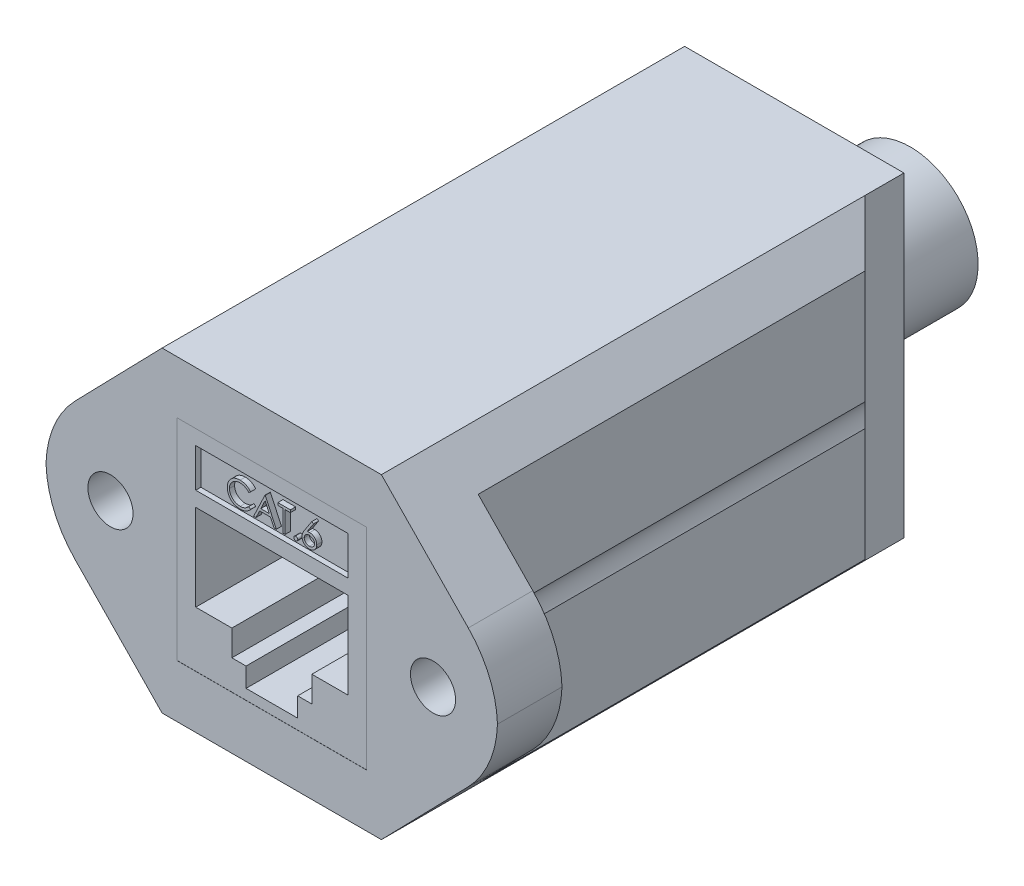
SolidWorks part; units mm, degrees
ref_plane "Front Plane" through (0, 0, 0) normal (0, 0, 1) x (1, 0, 0)
ref_plane "Top Plane" through (0, 0, 0) normal (0, 1, 0) x (1, 0, 0)
ref_plane "Right Plane" through (0, 0, 0) normal (1, 0, 0) x (0, 0, -1)
sketch "Sketch2" plane through (0, 0, 0) normal (0, 0, 1) x (1, 0, 0)
  line L0 (0, 0) -> (0, 24.5) construction
  line L1 (0, 24.5) -> (35, 24.5) construction
  line L2 (35, 24.5) -> (35, 0) construction
  line L3 (35, 0) -> (0, 0) construction
  line L4 (9, 0) -> (0, 9.25)
  line L5 (0, 9.25) -> (0, 15.25)
  line L6 (0, 15.25) -> (9, 24.5)
  line L7 (9, 24.5) -> (26, 24.5)
  line L8 (26, 24.5) -> (35, 15.25)
  line L9 (35, 15.25) -> (35, 9.25)
  line L10 (35, 9.25) -> (26, 0)
  line L11 (26, 0) -> (9, 0)
  line L12 (17.5, 24.5) -> (17.5, 0) construction
  line L13 (0, 12.25) -> (35, 12.25) construction
  dimension "D1" = 24.5
  dimension "D2" = 35
  dimension "D3" = 17
  dimension "D4" = 6
extrude "Boss-Extrude1" add sketch "Sketch2" along normal blind 5
fillet "Fillet1" radius 8 4 edges at (35, 9.25, 2.5) (35, 15.25, 2.5) (0, 9.25, 2.5) (0, 15.25, 2.5)
sketch "Sketch4" plane through (0, 0, 0) normal (0, 0, -1) x (-1, 0, 0)
  line L0 (-17.5, 24.5) -> (-17.5, 0) construction
  line L1 (-26, 24.5) -> (-9, 24.5) construction
  line L2 (-9, 0) -> (-26, 0) construction
  line L3 (-32.7338, 17.5791) -> (-26, 24.5) construction
  line L5 (-28.5, 21.9306) -> (-28.5, 2.5694)
  line L7 (-6.5, 21.9306) -> (-6.5, 2.5694)
  line L9 (-9, 24.5) -> (-2.2662, 17.5791) construction
  line L10 (-26, 0) -> (-32.7338, 6.9209) construction
  line L11 (-28.5, 21.9306) -> (-26, 24.5)
  line L12 (-26, 24.5) -> (-9, 24.5)
  line L13 (-9, 24.5) -> (-6.5, 21.9306)
  line L14 (-28.5, 2.5694) -> (-26, 0)
  line L15 (-26, 0) -> (-9, 0)
  line L16 (-9, 0) -> (-6.5, 2.5694)
  dimension "D1" = 22
extrude "Boss-Extrude2" add sketch "Sketch4" along normal blind 30
sketch "Sketch5" plane through (0, 0, -30) normal (0, 0, -1) x (-1, 0, 0)
  line L0 (-9, 24.5) -> (-26, 24.5) construction
  line L1 (-26, 0) -> (-9, 0) construction
  line L2 (-9, 24.5) -> (-26, 24.5)
  line L3 (-26, 0) -> (-9, 0)
  line L4 (-26, 0) -> (-26, 24.5)
  line L5 (-9, 0) -> (-9, 24.5)
extrude "Boss-Extrude3" add sketch "Sketch5" along normal blind 5.5
chamfer "Chamfer2" distance 2.5 angle 45 2 edges at (9, 12.25, -30) (26, 12.25, -30)
sketch "Sketch6" plane through (0, 0, -35.5) normal (0, 0, -1) x (-1, 0, 0)
  line L0 (-17.5, 24.5) -> (-17.5, 0) construction
  line L1 (-9, 24.5) -> (-26, 24.5) construction
  line L2 (-26, 0) -> (-9, 0) construction
  circle A0 centre (-17.5, 12.25) radius 5.25
  dimension "D1" = 10.5
extrude "Boss-Extrude4" add sketch "Sketch6" along normal blind 9
sketch "Sketch7" plane through (0, 0, 5) normal (0, 0, 1) x (1, 0, 0)
  line L0 (17.5, 24.5) -> (17.5, 0) construction
  line L1 (26, 24.5) -> (9, 24.5) construction
  line L2 (9, 0) -> (26, 0) construction
  line L3 (0.0039, 12.25) -> (34.9961, 12.25) construction
  line L4 (10.15, 20.4) -> (24.85, 20.4)
  line L5 (10.15, 20.4) -> (10.15, 4.1)
  line L6 (10.15, 4.1) -> (24.85, 4.1)
  line L7 (24.85, 20.4) -> (24.85, 4.1)
  dimension "D1" = 16.3
  dimension "D2" = 14.7
extrude "Cut-Extrude1" cut sketch "Sketch7" against normal blind 0.01
sketch "Sketch10" plane through (0, 0, 5) normal (0, 0, 1) x (1, 0, 0)
  line L0 (17.5, 24.5) -> (17.5, 0) construction
  line L1 (26, 24.5) -> (9, 24.5) construction
  line L2 (9, 0) -> (26, 0) construction
  line L3 (0.0039, 12.25) -> (34.9961, 12.25) construction
  circle A0 centre (5, 12.25) radius 1.75
  circle A1 centre (30, 12.25) radius 1.75
  dimension "D1" = 3.5
  dimension "D2" = 3.5
  dimension "D3" = 25
extrude "Cut-Extrude2" cut sketch "Sketch10" against normal through all
sketch "Sketch11" plane through (0, 0, 4.99) normal (0, 0, 1) x (1, 0, 0)
  line L0 (17.5, 20.4) -> (17.5, 4.1) construction
  line L1 (24.85, 20.4) -> (10.15, 20.4) construction
  line L2 (10.15, 4.1) -> (24.85, 4.1) construction
  line L3 (10.15, 12.25) -> (24.85, 12.25) construction
  line L4 (10.15, 20.4) -> (10.15, 4.1) construction
  line L5 (24.85, 4.1) -> (24.85, 20.4) construction
  line L6 (20.6, 8.4) -> (23.4, 8.4)
  line L7 (11.6, 15.1) -> (23.4, 15.1)
  line L8 (11.6, 15.1) -> (11.6, 8.4)
  line L9 (11.6, 8.4) -> (14.4, 8.4)
  line L10 (23.4, 15.1) -> (23.4, 8.4)
  line L11 (19.5, 6.4) -> (20.6, 6.4)
  line L12 (14.4, 8.4) -> (14.4, 6.4)
  line L13 (14.4, 6.4) -> (15.5, 6.4)
  line L14 (20.6, 8.4) -> (20.6, 6.4)
  line L16 (15.5, 6.4) -> (15.5, 4.9)
  line L17 (15.5, 4.9) -> (19.5, 4.9)
  line L18 (19.5, 6.4) -> (19.5, 4.9)
  dimension "D1" = 11.8
  dimension "D2" = 6.7
  dimension "D3" = 6.2
  dimension "D4" = 4
  dimension "D5" = 2
  dimension "D6" = 1.5
  dimension "D7" = 5.3
extrude "Cut-Extrude3" cut sketch "Sketch11" against normal blind 11
sketch "Sketch12" plane through (0, 0, 4.99) normal (0, 0, 1) x (1, 0, 0)
  line L0 (11.6, 15.1) -> (11.6, 8.4) construction
  line L1 (11.6, 16.25) -> (23.4, 16.25)
  line L2 (11.6, 16.25) -> (11.6, 19.25)
  line L3 (11.6, 19.25) -> (23.4, 19.25)
  line L4 (23.4, 16.25) -> (23.4, 19.25)
  line L5 (23.4, 8.4) -> (23.4, 15.1) construction
  line L6 (17.5, 15.1) -> (17.5, 20.4) construction
  line L7 (23.4, 15.1) -> (11.6, 15.1) construction
  line L8 (24.85, 20.4) -> (10.15, 20.4) construction
  line L9 (17.5, 17.75) -> (24.85, 17.75) construction
  line L10 (24.85, 4.1) -> (24.85, 20.4) construction
  dimension "D1" = 3
extrude "Cut-Extrude4" cut sketch "Sketch12" against normal blind 0.4
sketch "Sketch13" plane through (0, 0, 4.59) normal (0, 0, 1) x (1, 0, 0)
  line L0 (11.6, 16.75) -> (23.4, 16.75) construction
  line L1 (11.6, 19.25) -> (11.6, 16.25) construction
  line L2 (23.4, 16.25) -> (23.4, 19.25) construction
  line L3 (11.6, 16.25) -> (23.4, 16.25) construction
  text T0 "CAT.6" font "Century Gothic" height in points 7
  dimension "D1" = 0.5
extrude "Boss-Extrude5" add sketch "Sketch13" along normal blind 0.4
ref_plane "Plane1" through (17.5, 0, 0) normal (1, 0, 0) x (0, 0, -1)
